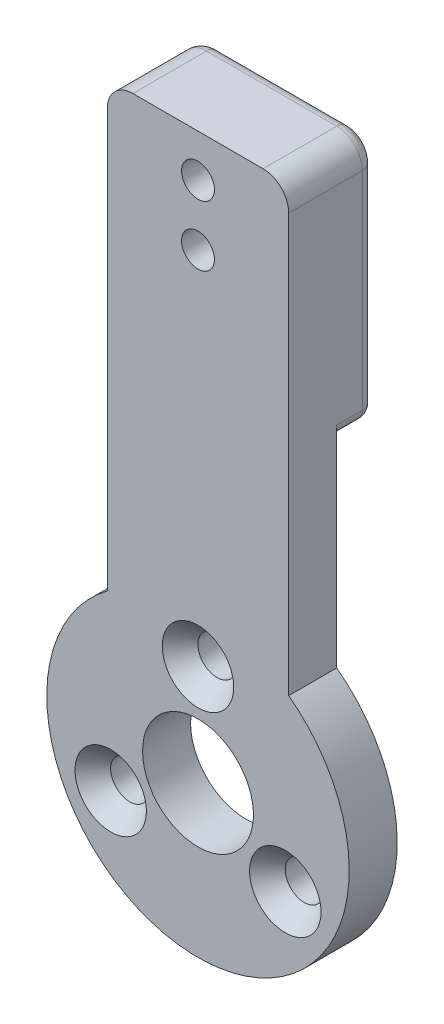
SolidWorks part; units mm, degrees
material "Nickel"
ref_plane "Front Plane" through (0, 0, 0) normal (0, 0, 1) x (1, 0, 0)
ref_plane "Top Plane" through (0, 0, 0) normal (0, 1, 0) x (1, 0, 0)
ref_plane "Right Plane" through (0, 0, 0) normal (1, 0, 0) x (0, 0, -1)
sketch "Sketch1" plane through (0, 0, 0) normal (0, 0, 1) x (1, 0, 0)
  line L0 (0, 15) -> (0, 56) construction
  line L1 (-9, 56) -> (9, 56)
  line L3 (9, 56) -> (9, 12)
  line L4 (-9, 56) -> (-9, 12)
  circle A0 centre (0, 0) radius 15
  circle A1 centre (0, 0) radius 5.5
  circle A2 centre (0, 0) radius 32.5
  dimension "D1" = 30
  dimension "D2" = 11
  dimension "D5" = 65
  dimension "D3" = 44
  dimension "D4" = 18
extrude "Body" add sketch "Sketch1" along normal blind 4.7625 contours A0 A1 | A0 L0 L4 | L0 A0 L3 | A2 L0 L1 L4 | L0 A2 L3 L1 region at (-4.5692, 23.0443, 0) region at (4.5692, 23.0443, 0) region at (4.6093, 13.8278, 0) region at (-4.5397, 44.0369, 0) region at (4.5397, 44.0369, 0)
extrude "Hex NutyFoot" add sketch "Sketch1<3>" against normal blind 3.81 contours L0 A2 L3 L1 | A2 L0 L1 L4 region at (-4.5397, 44.0369, 0) region at (4.5397, 44.0369, 0)
sketch "Sketch1<3>" plane through (0, 0, 0) normal (0, 0, 1) x (1, 0, 0) same geometry as "Sketch1"
hole_wizard "#4 Clearance Hole1" positions "3DSketch3" profile "Sketch4" hole size "#4" standard "ANSI Inch" end condition through all
sketch3d "3DSketch3"
  line L3 (-9, 45.78, 4.7625) -> (9, 45.78, 4.7625) construction
  line L4 (-9, 56, 4.7625) -> (-9, 12, 4.7625) construction
  line L5 (9, 56, 4.7625) -> (9, 12, 4.7625) construction
  line L7 (-9, 51.78, 4.7625) -> (9, 51.78, 4.7625) construction
  line L8 (-9, 56, 4.7625) -> (-9, 12, 4.7625) construction
  line L9 (9, 56, 4.7625) -> (9, 12, 4.7625) construction
  line L10 (0, 0, 4.7625) -> (0, 0, 0) construction
  line L11 (0, 0, 4.7625) -> (0, 0, 0) construction
  line L12 (0, 15, 4.7625) -> (-9, 15, 4.7625) construction
  line L13 (0, 15, 4.7625) -> (9, 15, 4.7625) construction
  line L15 (0, 0, 4.7625) -> (0, 0, 0) construction
  line L17 (0, 15, 4.7625) -> (0, 0, 4.7625) construction
  circle A0 centre (0, 0, 4.7625) radius 15 construction
  point P0 (0, 45.78, 4.7625)
  point P32 (0, 51.78, 4.7625)
  point P35 (0, 0, 19.7625)
  dimension "D3" = 30
  dimension "D1" = 30.78
  dimension "D2" = 6
sketch "Sketch4" plane through (0, 45.78, 4.7625) normal (1, 0, 0) x (0, -1, 0)
  line L0 (0, 0) -> (0, 8.5725)
  line L1 (0, 8.5725) -> (1.6319, 8.5725)
  line L2 (1.6319, 8.5725) -> (1.6319, 0)
  line L5 (1.6319, 0) -> (0, 0)
  line L11 (0, -6.35) -> (0, 107.95) construction
  dimension "Thru Hole Dia." = 3.2639
  dimension "Thru Hole Depth" = 8.5725
sketch "Sketch7" plane through (0, 0, -3.81) normal (0, 0, -1) x (-1, 0, 0)
  line L0 (-2.667, 45.78) -> (2.667, 45.78)
  line L1 (-2.667, 51.78) -> (2.667, 51.78)
  line L2 (-1.3335, 49.4703) -> (1.3335, 54.0897)
  line L3 (1.3335, 49.4703) -> (-1.3335, 54.0897)
  line L4 (-1.3335, 54.0897) -> (1.3335, 54.0897)
  line L5 (1.3335, 54.0897) -> (2.667, 51.78)
  line L6 (2.667, 51.78) -> (1.3335, 49.4703)
  line L7 (1.3335, 49.4703) -> (-1.3335, 49.4703)
  line L8 (-1.3335, 49.4703) -> (-2.667, 51.78)
  line L9 (-2.667, 51.78) -> (-1.3335, 54.0897)
  line L10 (-1.3335, 43.4703) -> (1.3335, 48.0897)
  line L11 (1.3335, 43.4703) -> (-1.3335, 48.0897)
  line L12 (-1.3335, 48.0897) -> (1.3335, 48.0897)
  line L13 (1.3335, 48.0897) -> (2.667, 45.78)
  line L14 (2.667, 45.78) -> (1.3335, 43.4703)
  line L15 (1.3335, 43.4703) -> (-1.3335, 43.4703)
  line L16 (-1.3335, 43.4703) -> (-2.667, 45.78)
  line L17 (-2.667, 45.78) -> (-1.3335, 48.0897)
  circle A0 centre (0, 51.78) radius 1.6319
  circle A1 centre (0, 51.78) radius 2.667
  circle A2 centre (0, 51.78) radius 1.6319 construction
  circle A3 centre (0, 45.78) radius 1.6319
  circle A4 centre (0, 45.78) radius 2.667
  circle A5 centre (0, 45.78) radius 1.6319 construction
  circle M1 centre (0, 45.78) radius 1.6319
  circle M2 centre (0, 51.78) radius 1.6319
  dimension "D2" = 1.632
  dimension "D3" = 5.334
  dimension "D1" = 1.632
  dimension "D6" = 5.334
  dimension "D4" = 60
  dimension "D5" = 60
  dimension "D7" = 60
  dimension "D8" = 60
extrude "Hex Nut Recess" cut sketch "Sketch7" against normal blind 3.048 contours L5 L2 L1 M2 | L6 L1 L3 M2 | L7 L3 L2 M2 | L8 L2 L1 M2 | L9 L1 L3 M2 | L4 L3 L2 M2 | L13 L10 L0 M1 | L14 L0 L11 M1 | L15 L11 L10 M1 | L16 L10 L0 M1 | L17 L0 L11 M1 | L12 L11 L10 M1 region at (-1.6924, 46.7571, -3.81) region at (-1.6924, 44.8029, -3.81) region at (0, 47.7342, -3.81) region at (0, 43.8258, -3.81) region at (1.6924, 44.8029, -3.81) region at (1.6924, 46.7571, -3.81) region at (-1.6924, 52.7571, -3.81) region at (-1.6924, 50.8029, -3.81) region at (0, 53.7342, -3.81) region at (0, 49.8258, -3.81) region at (1.6924, 50.8029, -3.81) region at (1.6924, 52.7571, -3.81)
hole_wizard "CSK for #6 Flat Head Machine Screw1" positions "3DSketch2" profile "Sketch3" countersink size "#6" standard "Ansi Inch" end condition through all
sketch3d "3DSketch2"
  line L16 (0, 0, 4.7625) -> (0, 0, 0) construction
  line L17 (0, 0, 4.7625) -> (0, 0, 0) construction
  line L18 (0, 0, 4.7625) -> (0, 15, 4.7625) construction
  line L19 (0, 0, 4.7625) -> (-12.9904, -7.5, 4.7625) construction
  line L20 (0, 0, 4.7625) -> (12.9904, -7.5, 4.7625) construction
  circle A6 centre (0, 0, 4.7625) radius 15
  circle A7 centre (0, 0, 4.7625) radius 10
  point P73 (0, 10, 4.7625)
  point P75 (8.6603, -5, 4.7625)
  point P77 (-8.6603, -5, 4.7625)
  point P87 (0, 0, 19.7625)
  point P94 (0, 0, 14.7625)
  dimension "D3" = 120
  dimension "D1" = 20
  dimension "D4" = 30
  dimension "D2" = 120
sketch "Sketch3" plane through (0, 10, 4.7625) normal (1, 0, 0) x (0, -1, 0)
  line L0 (0, 0) -> (0, 8.5725)
  line L1 (0, 8.5725) -> (1.8986, 8.5725)
  line L2 (1.8986, 8.5725) -> (1.8986, 1.892)
  line L3 (1.8986, 1.892) -> (3.5433, 0)
  line L5 (3.5433, 0) -> (0, 0)
  line L6 (-1.8986, 1.892) -> (-3.5433, 0) construction
  line L11 (0, -6.35) -> (0, 107.95) construction
  dimension "Thru Hole Dia." = 3.7973
  dimension "Thru Hole Depth" = 8.5725
  dimension "Near C'Sink Dia." = 7.0866
  dimension "Near C'Sink Angle" = 82
fillet "Fillet1" radius 2.54 2 edges at (-9, 56, 0.4763) (9, 56, 0.4763)
fillet "Fillet2" radius 1.27 8 edges at (-9, 42.3445, -3.81) (-8.2561, 55.2561, -3.81) (0, 56, -3.81) (8.2561, 55.2561, -3.81) (0, 32.5, -3.81) (9, 42.3445, -3.81)
